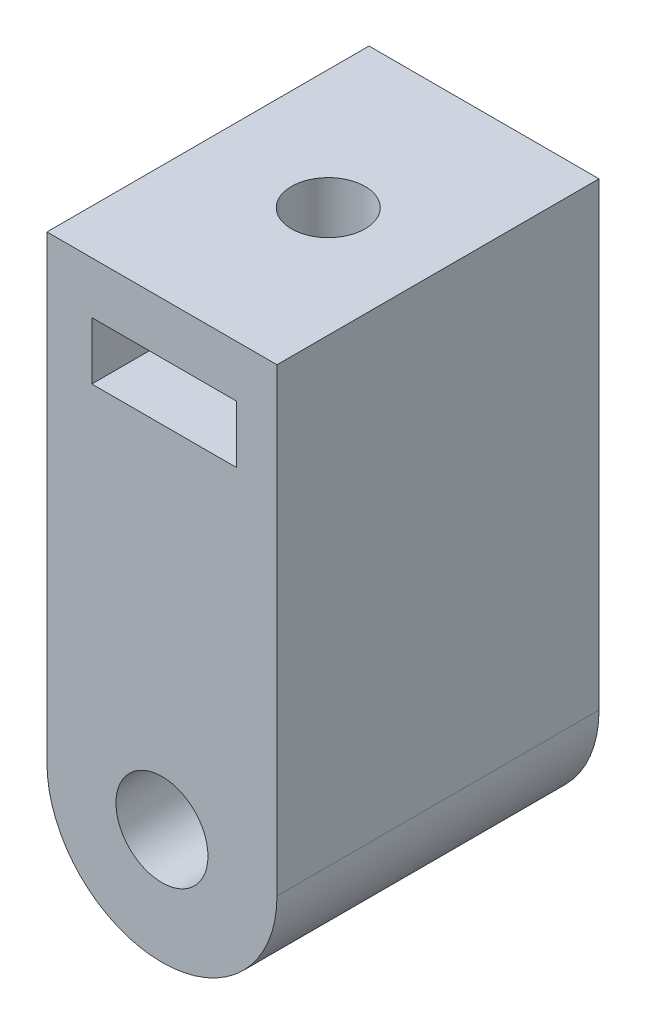
SolidWorks part; units mm, degrees
ref_plane "Спереди" through (0, 0, 0) normal (0, 0, 1) x (1, 0, 0)
ref_plane "Сверху" through (0, 0, 0) normal (0, 1, 0) x (1, 0, 0)
ref_plane "Справа" through (0, 0, 0) normal (1, 0, 0) x (0, 0, -1)
sketch "Эскиз1" plane through (0, 0, 0) normal (0, 0, 1) x (1, 0, 0)
  circle A0 centre (0, 0) radius 2
  circle A1 centre (0, 0) radius 5
extrude "Бобышка-Вытянуть1" add sketch "Эскиз1" along normal blind 14
sketch "Эскиз2" plane through (0, 0, 14) normal (0, 0, 1) x (1, 0, 0)
  line L0 (-5, 0) -> (-2, 0)
  line L2 (-5, 0) -> (-5, 20)
  line L3 (-5, 20) -> (5, 20)
  line L4 (5, 0) -> (5, 20)
  line L5 (0.4851, 1.9403) -> (5, 20) construction
  line L6 (-5, 20) -> (-0.4851, 1.9403) construction
  line L7 (2, 0) -> (5, 0)
  arc A0 (2, 0) -> (-2, 0) centre (0, 0) ccw
  point P0 (0, 0)
  point P9 (0, 0)
extrude "Бобышка-Вытянуть2" add sketch "Эскиз2" against normal up to surface (14 mm away) up to face at (5, 0, 0)
sketch "Эскиз5" plane through (0, 0, 14) normal (0, 0, 1) x (1, 0, 0)
  line L1 (3.25, 17.75) -> (-3.05, 17.75)
  line L2 (3.25, 17.75) -> (3.25, 15.25)
  line L3 (3.25, 15.25) -> (-3.05, 15.25)
  line L4 (-3.05, 17.75) -> (-3.05, 15.25)
  line L5 (3.25, 17.75) -> (-3.05, 15.25) construction
  line L6 (3.25, 15.25) -> (-3.05, 17.75) construction
  point P0 (0.1, 16.5)
extrude "Вырез-Вытянуть3" cut sketch "Эскиз5" against normal blind 10
sketch "Эскиз8" plane through (0, 15.25, 0) normal (0, 1, 0) x (1, 0, 0)
  line L0 (-3.05, -14) -> (-5.0865, -14)
sketch "Эскиз10" plane through (-5, 0, 0) normal (-1, 0, 0) x (0, 0, 1)
  line L0 (12.5, 3.2685) -> (14, 3.2685) construction
  line L1 (1.4417, 2.925) -> (12.5, 2.925)
  line L2 (1.4417, 2.925) -> (1.4417, 12.975)
  line L3 (1.4417, 12.975) -> (12.5, 12.975)
  line L4 (12.5, 2.925) -> (12.5, 12.975)
  line L5 (1.4417, 2.925) -> (12.5, 12.975) construction
  line L6 (1.4417, 12.975) -> (12.5, 2.925) construction
  line L7 (14, 20) -> (14, 0) construction
  line L8 (6.9709, 7.95) -> (12.5, 7.95) construction
  line L9 (6.9709, 2.925) -> (14, 2.925) construction
  line L10 (0, 0) -> (0, 20) construction
  point P0 (6.9709, 7.95)
  point P12 (0, 0)
  dimension "D1" = 1.4417
extrude "Вырез-Вытянуть5" cut sketch "Эскиз10" against normal blind 9.4
sketch "Эскиз12" plane through (0, 2.925, 0) normal (0, 1, 0) x (1, 0, 0)
  line L0 (0.1995, -1.4417) -> (0.1995, -12.5) construction
  line L1 (4.4, -1.4417) -> (-5, -1.4417) construction
  line L2 (4.4, -12.5) -> (-5, -12.5) construction
  line L3 (-5, -6.9709) -> (4.4, -6.9709) construction
  line L4 (-5, -1.4417) -> (-5, -12.5) construction
  line L5 (4.4, -1.4417) -> (4.4, -12.5) construction
  circle A0 centre (0.1995, -6.9709) radius 1.6
extrude "Вырез-Вытянуть7" cut sketch "Эскиз12" along normal through all
sketch "Эскиз13" plane through (0, 15.25, 0) normal (0, 1, 0) x (1, 0, 0)
  line L0 (-1.3858, -4.2257) -> (-1.3858, -4)
  line L1 (3.3695, -6.9706) -> (1.7842, -4.2254)
  line L2 (1.7842, -4.2254) -> (-1.3858, -4.2257)
  line L3 (-1.3858, -4.2257) -> (-2.9705, -6.9711)
  line L4 (-2.9705, -6.9711) -> (-1.3853, -9.7163)
  line L5 (-1.3853, -9.7163) -> (1.7847, -9.716)
  line L6 (1.7847, -9.716) -> (3.3695, -6.9706)
  line L7 (3.25, -4) -> (-3.05, -4) construction
  line L8 (3.3308, -6.9706) -> (3.3695, -6.9706)
  circle A0 centre (0.1995, -6.9709) radius 3.17 construction
